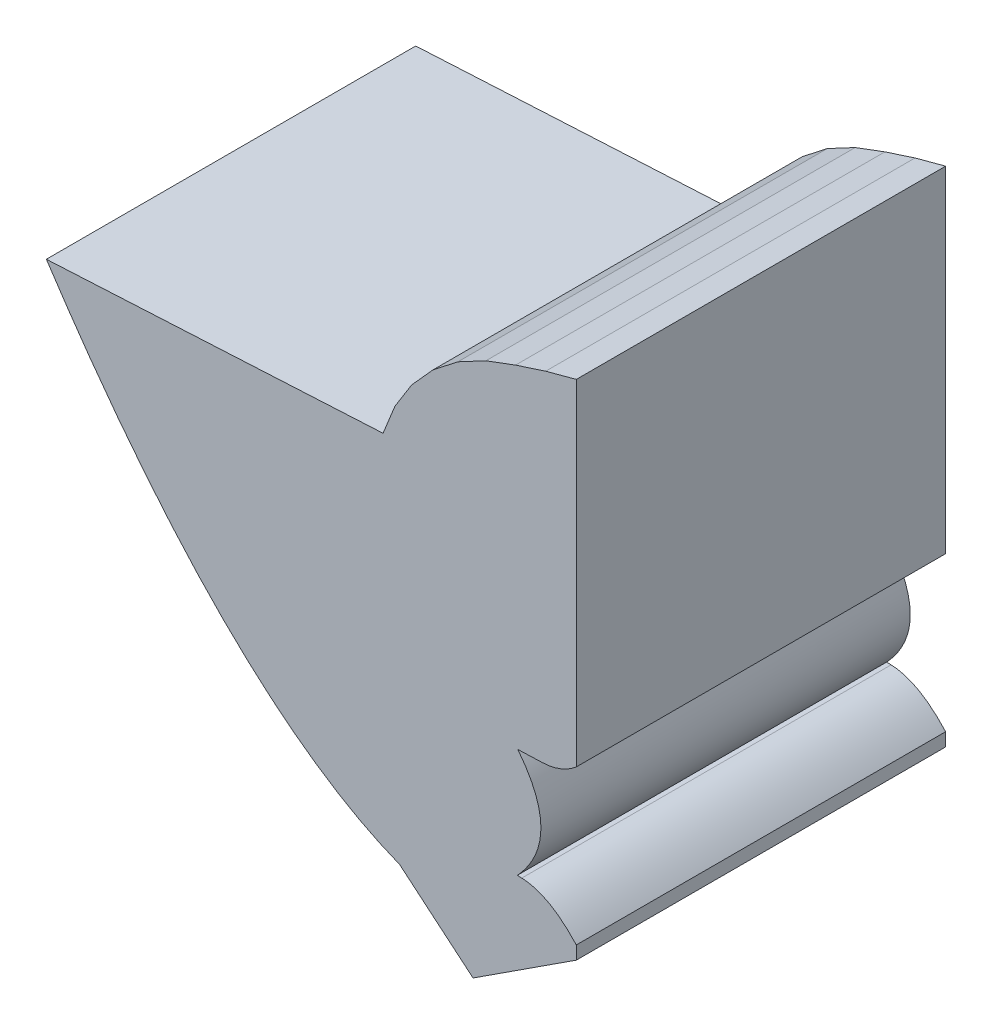
SolidWorks part; units mm, degrees
ref_plane "Alzado" through (0, 0, 0) normal (0, 0, 1) x (1, 0, 0)
ref_plane "Planta" through (0, 0, 0) normal (0, 1, 0) x (1, 0, 0)
ref_plane "Vista lateral" through (0, 0, 0) normal (1, 0, 0) x (0, 0, -1)
sketch "Croquis1" plane through (0, 0, 0) normal (0, 0, 1) x (1, 0, 0)
  line L0 (-8.9818, 12.6082) -> (-23.0359, 11.8716) construction
  line L1 (-8.9818, 12.6082) -> (-23.0359, 11.8716)
  line L2 (-8.9818, 12.6082) -> (-23.0359, 11.8716) construction
  line L3 (-2.1773, 6.1864) -> (-2.1773, -4.6845)
  line L4 (-8.9818, 12.6082) -> (-23.0359, 11.8716)
  line L6 (-1.3949, 1.9763) -> (0.3551, 2.2848) construction
  line L7 (-1.3949, 1.9763) -> (0.3551, 2.2848) construction
  line L8 (0.3551, 2.2848) -> (0.3551, 2.8423) construction
  line L9 (0.3551, 2.2848) -> (0.3551, 3.0015) construction
  line L10 (0.3551, -2.2848) -> (-1.3949, -2.2237) construction
  line L11 (0.3551, -2.2848) -> (-1.3949, -2.2237) construction
  line L12 (0.3551, 2.2848) -> (0.3551, -2.2848) construction
  line L13 (0.3551, -2.2848) -> (0.3551, -2.7233) construction
  line L14 (-8.9818, 12.6082) -> (-6.9949, 10.4774)
  line L15 (-23.0359, 11.5401) -> (-23.0359, 11.8716) construction
  line L16 (-23.0359, 11.5401) -> (-23.0359, 11.8716)
  arc A0 (-18.9452, 7.5409) -> (-23.0359, 11.5401) centre (-69.8841, -40.4718) ccw construction
  arc A1 (-18.9452, 7.5409) -> (-23.0359, 11.5401) centre (-69.8841, -40.4718) ccw
  spline S1 degree 2 poles (-4119.0151, 24659.0515) (3413.1083, -24757.661) (-2705.4818, 24835.5983) knots 0.405517 0.405517 0.405517 0.594449 0.594449 0.594449 weights 1 1 1 only from (-18.9452, 7.5409) to (-2.8466, -5.0591) construction
  spline S2 degree 2 poles (-18.9452, 7.5409) (-10.215, -3.6976) (-2.8466, -5.0591) knots 0.497667 0.497667 0.497667 0.499554 0.499554 0.499554 weights 1 1 1
  spline S3 degree 2 poles (-23607.9882, 8212.1168) (23492.4763, -8550.6979) (-23372.6553, 8887.1675) knots 0.40552 0.40552 0.40552 0.594498 0.594498 0.594498 weights 1 1 1 only from (0.3551, 3.0015) to (-6.9949, 10.4774) construction
  spline S4 degree 2 poles (-2.1773, 6.1864) (-4.0633, 8.1416) (-6.9949, 10.4774) knots 0.501383 0.501383 0.501383 0.502013 0.502013 0.502013 weights 1 1 1
  spline S5 degree 2 poles (-1.3949, -2.2237) (-0.9075, -0.1237) (-1.3949, 1.9763) knots 0 0 0 1 1 1 weights 1 3.231801 1 construction
  spline S6 degree 2 poles (-1.3949, -2.2237) (-0.9075, -0.1237) (-1.3949, 1.9763) knots 0 0 0 1 1 1 weights 1 3.231801 1 construction
  spline S7 degree 2 poles (-24934.0908, 1769.912) (24899.5391, -2178.5787) (-24858.838, 2586.1022) knots 0.405518 0.405518 0.405518 0.594474 0.594474 0.594474 weights 1 1 1 only from (-2.8466, -5.0591) to (0.3551, -2.7233) construction
  spline S8 degree 2 poles (-2.8466, -5.0591) (-2.4982, -4.873) (-2.1773, -4.6845) knots 0.498812 0.498812 0.498812 0.498912 0.498912 0.498912 weights 1 1 1
extrude "croquis base" add sketch "Croquis1" along normal mid plane 13.9874 contours S2 S8 L13 L11 S6 L7 L9 S4 L14 L1 L16 A1 region at (-10.1535, 5.1597, 0)
sketch "Croquis6" plane through (0, 0, 0) normal (1, 0, 0) x (0, 0, -1)
  line L0 (6.9937, 12.6082) -> (6.9937, 10.4774) construction
  line L1 (6.9937, 12.6082) -> (6.9937, -5.0591)
  line L2 (-6.9937, 12.6082) -> (-6.9937, 10.4774) construction
  line L3 (-6.9937, 12.6082) -> (-6.9937, -5.0591)
  line L4 (-6.9937, -5.0591) -> (6.9937, -5.0591) construction
  line L5 (-6.9937, -5.0591) -> (-4.9937, -5.0591)
  line L6 (6.9937, 12.6082) -> (4.9937, -5.0591)
  line L7 (-6.9937, 12.6082) -> (-4.9937, -5.0591)
  line L8 (4.9937, -5.0591) -> (6.9937, -5.0591)
  dimension "D1" = 2
  dimension "D2" = 2
sketch "Croquis9" plane through (0, 0, 0) normal (0, 0, 1) x (1, 0, 0)
  line L0 (0, 0) -> (-4.9559, 0) construction
  line L1 (-2.4454, 0.1046) -> (-1.25, 0) construction
  line L2 (-1.25, 0) -> (-1.25, -4.2203) construction
  line L3 (-2.1773, -1.8404) -> (-2.1773, -4.3883)
  line L4 (-2.1773, 6.1864) -> (-2.1773, -4.6845) construction
  line L5 (-2.4454, 0.1046) -> (-2.0532, -4.3783) construction
  line L6 (-2.4454, 0.1046) -> (-15.184, 3.0892) construction
  line L7 (-19.6099, 15.4015) -> (-15.184, 3.0892) construction
  line L9 (-15.184, 3.0892) -> (-25.9078, 12.6462) construction
  line L10 (-15.184, 3.0892) -> (-13.3572, 5.139) construction
  line L11 (-19.9694, 9.4938) -> (-10.3098, 10)
  line L12 (-10.3098, 10) -> (-2.1773, 6.0829)
  line L13 (-2.1773, 6.0829) -> (-2.1773, 2.4242)
  line L15 (-2.1773, 6.1864) -> (-2.1773, -4.6845) construction
  parabola Q0 (-2.1773, 2.4242) -> (-2.1773, -1.8404) focus (-2.4454, 0.1046) apex (-1.25, 0)
  parabola Q1 (-2.1773, -4.3883) -> (-19.9694, 9.4938) focus (-2.4454, 0.1046) apex (-2.0532, -4.3783)
  spline S0 degree 2 poles (-18.9452, 7.5409) (-10.215, -3.6976) (-2.8466, -5.0591) knots 0.497667 0.497667 0.497667 0.499554 0.499554 0.499554 weights 1 1 1 construction
  dimension "D1" = 95
  dimension "D2" = 1.25
  dimension "D3" = 1.2
  dimension "D4" = 4.5
  dimension "D5" = 5
  dimension "D6" = 3
  dimension "D7" = 10
extrude "lente ppal 1" add sketch "Croquis9" along normal up to surface and the other way up to surface contours Q1 L3 Q0 L13 L12 L11 region at (-9.1064, 3.5992, 0) up to face at (-11.7662, 6.8113, 6.9937) other way up to face at (-11.7662, 6.8113, -6.9937)
extrude "lente ppal 2" cut sketch "Croquis9<3>" against normal through all both and the other way through all flip side to cut
sketch "Croquis9<3>" plane through (0, 0, 0) normal (0, 0, 1) x (1, 0, 0) same geometry as "Croquis9"
sketch "Croquis8" plane through (0, 0, 0) normal (0, 0, 1) x (1, 0, 0)
  line L0 (-8.9818, 12.6082) -> (-23.0359, 11.8716) construction
  line L1 (-10.3098, 10) -> (0.1, 15.5879) construction
  line L3 (0.1, 2.8777) -> (0.1, 15.5879)
  line L5 (-7.2179, 10.162) -> (-6.7684, 11.2747)
  line L6 (-6.7684, 11.2747) -> (-6.1325, 12.2923)
  line L7 (-6.1325, 12.2923) -> (-5.3295, 13.1841)
  line L8 (-5.3295, 13.1841) -> (-4.3839, 13.9229)
  line L9 (-4.3839, 13.9229) -> (-3.3244, 14.4863)
  line L10 (-3.3244, 14.4863) -> (-2.2004, 14.9065)
  line L11 (-2.2004, 14.9065) -> (-1.0591, 15.2773)
  line L12 (-1.0591, 15.2773) -> (0.1, 15.5879)
  line L13 (-0.5, 2) -> (-9.2621, 13.0152) construction
  line L14 (-9.2621, 13.0152) -> (-9.6721, 13.4466) construction
  line L15 (-9.2621, 13.0152) -> (-9.8313, 13.8617) construction
  line L16 (-0.5, 2) -> (-6.9932, 10.7183) construction
  line L17 (-6.9932, 10.7183) -> (-9.8657, 11.8789) construction
  line L18 (-0.5, 2) -> (-6.4504, 11.7835) construction
  line L19 (-1.1905, 2.3769) -> (-13.6677, 1.9412) construction
  line L20 (-6.4504, 11.7835) -> (-8.5297, 13.0828) construction
  line L21 (-0.5, 2) -> (-5.731, 12.7382) construction
  line L22 (-0.5, 2) -> (-4.8567, 13.5535) construction
  line L23 (-4.8567, 13.5535) -> (-7.2264, 16.5865) construction
  line L24 (-0.5, 2) -> (-3.8542, 14.2046) construction
  line L25 (-3.8542, 14.2046) -> (-5.6175, 17.521) construction
  line L26 (-0.5, 2) -> (-2.7624, 14.6964) construction
  line L27 (-2.7624, 14.6964) -> (-4.1395, 18.3795) construction
  line L28 (-0.5, 2) -> (-1.6297, 15.0919) construction
  line L29 (-1.6297, 15.0919) -> (-2.365, 17.3548) construction
  line L30 (-0.5, 2) -> (-0.4796, 15.4326) construction
  line L31 (-0.4796, 15.4326) -> (-1.0837, 17.6873) construction
  line L32 (-6.4504, 11.7835) -> (-9.194, 13.4978) construction
  line L33 (-5.731, 12.7382) -> (-8.3325, 15.0806) construction
  line L34 (-10.3098, 10) -> (-10.3098, 19.2428) construction
  line L35 (-0.4796, 15.4326) -> (-1.3923, 18.839) construction
  line L36 (-10.3098, 10) -> (-7.2179, 10.162)
  line L37 (-6.9932, 10.7183) -> (-7.7178, 13.8573) construction
  line L38 (-6.9932, 10.7183) -> (-7.6851, 10.9979) construction
  line L39 (-6.4504, 11.7835) -> (-7.328, 15.5847) construction
  line L40 (-6.4504, 11.7835) -> (-8.1247, 12.8297) construction
  line L41 (-5.731, 12.7382) -> (-6.4786, 15.9764) construction
  line L42 (-5.731, 12.7382) -> (-7.1919, 14.0536) construction
  line L43 (-4.8567, 13.5535) -> (-5.8037, 17.6554) construction
  line L44 (-4.8567, 13.5535) -> (-6.0786, 15.1174) construction
  line L45 (-3.8542, 14.2046) -> (-4.8235, 18.4032) construction
  line L46 (-3.8542, 14.2046) -> (-4.9673, 16.2982) construction
  line L47 (-2.7624, 14.6964) -> (-3.6965, 18.7423) construction
  line L48 (-2.7624, 14.6964) -> (-3.4418, 16.5134) construction
  line L49 (-0.5, 2) -> (-0.5437, 2.5) construction
  line L50 (-0.5437, 2.5) -> (-0.8858, 3.4397) construction
  line L51 (0, 0) -> (0, 1.5958) construction
  line L52 (0, 12.6082) -> (0, -5.0591) construction
  line L53 (-1.6297, 15.0919) -> (-2.8173, 18.7468) construction
  line L54 (-1.6297, 15.0919) -> (-2.2911, 17.9567) construction
  line L55 (-0.4796, 15.4326) -> (-1.0428, 17.8722) construction
  line L56 (-10.3098, 10) -> (-2.1773, 2.3425)
  line L57 (-2.1773, 2.3425) -> (-1.1905, 2.3769)
  line L58 (-10.3098, 10) -> (-19.9694, 9.4938) construction
  line L60 (-2.1773, 6.0829) -> (-10.3098, 10) construction
  parabola Q0 (-1.1905, 2.3769) -> (0.1, 2.8777) focus (-0.8858, 3.4397) apex (-0.5437, 2.5)
  spline S1 degree 2 poles (-10.3098, 10) (-2.4445, 4.1882) (-0.2283, 0.4324) knots 0.500548 0.500548 0.500548 0.502013 0.502013 0.502013 weights 1 1 1 construction
  dimension "D1" = 5.039
  dimension "D3" = 15
  dimension "D4" = 25
  dimension "D5" = 80
  dimension "D6" = 45
  dimension "D7" = 35
  dimension "D8" = 7.5
  dimension "D9" = 5
  dimension "D10" = 55
  dimension "D11" = 211.322
  dimension "D12" = 206.691
  dimension "D13" = 202.027
  dimension "D14" = 197.339
  dimension "D15" = 192.633
  dimension "D16" = 0.5
  dimension "D17" = 0.5
  dimension "D18" = 2
  dimension "D19" = 5
  dimension "D20" = 20
  dimension "D21" = 88
  dimension "D22" = 1
  dimension "D23" = 0.1
  dimension "D24" = 178
  dimension "D25" = 1.2
  dimension "D26" = 10
extrude "lente frontal" add sketch "Croquis8" along normal up to surface and the other way up to surface up to face at (-5.0154, 2.8272, 6.9937) other way up to face at (-7.9808, 4.4301, -6.9937)
sketch "Croquis11" plane through (0, 0, 0) normal (0, 0, 1) x (1, 0, 0)
  line L0 (0, 0) -> (0, -3.4622) construction
  line L1 (0, 0) -> (3.4097, 0) construction
  line L2 (0, 0) -> (-2, -1.8) construction
  line L4 (-2.0175, -2.7998) -> (-2, -1.8) construction
  line L5 (-1.9651, -1.8009) -> (-2.5941, -1.7789) construction
  line L7 (0.1, -2.9604) -> (0.1, -3.4604)
  line L8 (0.1, 2.8777) -> (0.1, 15.5879) construction
  line L14 (-1.9651, -1.8009) -> (-9.1124, -1.5513)
  line L15 (-9.1124, -1.5513) -> (-3.8107, -6)
  line L16 (-3.8107, -6) -> (-3.8107, 3.7291) construction
  line L17 (0.1, -3.4604) -> (-3.8107, -6)
  parabola Q0 (-1.9651, -1.8009) -> (0.1, -2.9604) focus (-2.0175, -2.7998) apex (-2, -1.8)
  dimension "D1" = 1.8
  dimension "D2" = 88
  dimension "D3" = 1
  dimension "D4" = 2
  dimension "D5" = 1
  dimension "D6" = 0.5
  dimension "D7" = 6
  dimension "D9" = 107
  dimension "D10" = 57
extrude "lente trasera" add sketch "Croquis11" along normal up to surface and the other way up to surface up to face at (-3.7041, 8.4573, 6.9937) other way up to face at (-4.8085, 9.1371, -6.9937)
